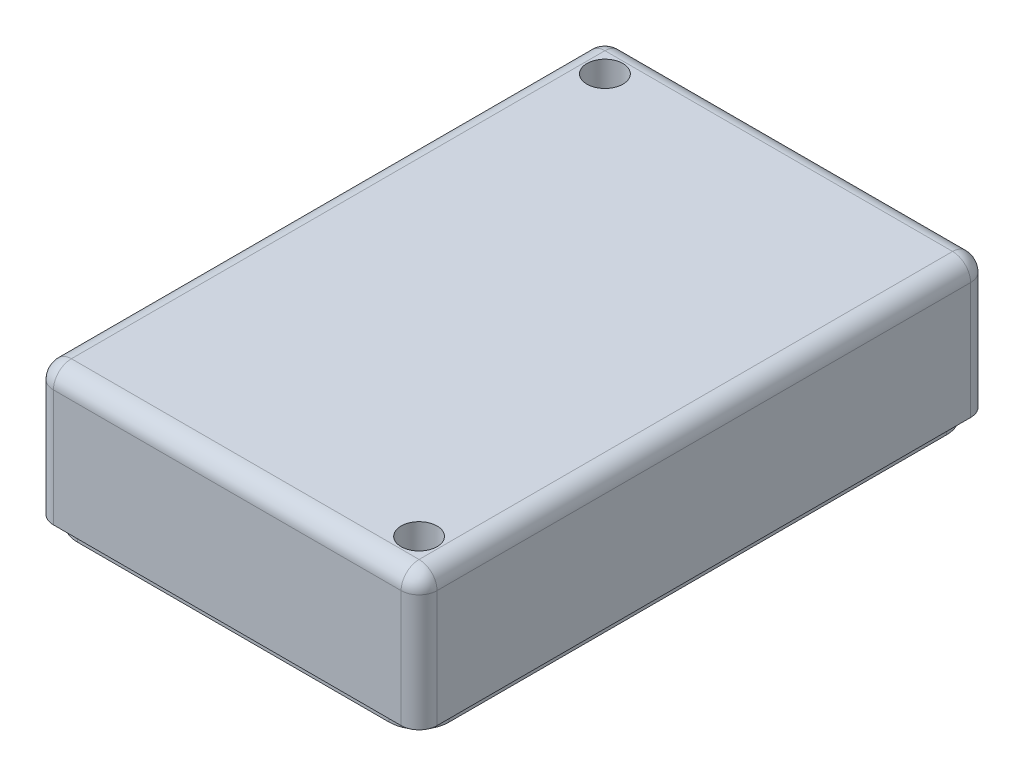
SolidWorks part; units mm, degrees
ref_plane "Front Plane" through (0, 0, 0) normal (0, 0, 1) x (1, 0, 0)
ref_plane "Top Plane" through (0, 0, 0) normal (0, 1, 0) x (1, 0, 0)
ref_plane "Right Plane" through (0, 0, 0) normal (1, 0, 0) x (0, 0, -1)
sketch "Sketch1" plane through (0, 0, 0) normal (0, 1, 0) x (1, 0, 0)
  line L5 (-32, -47.5) -> (32, -47.5)
  line L6 (-32, -47.5) -> (-32, 47.5)
  line L7 (-32, 47.5) -> (32, 47.5)
  line L8 (32, -47.5) -> (32, 47.5)
  line L9 (-32, -47.5) -> (32, 47.5) construction
  line L10 (-32, 47.5) -> (32, -47.5) construction
  point P0 (0, 0)
  dimension "D1" = 64
  dimension "D2" = 95
extrude "Boss-Extrude1" add sketch "Sketch1" along normal blind 2
sketch3d "3DSketch3"
  line L0 (-30, 0, 45.5) -> (-30, 0, -45.5)
  line L1 (-30, 0, -45.5) -> (30, 0, -45.5)
  line L2 (30, 0, -45.5) -> (30, 0, 45.5)
  line L3 (30, 0, 45.5) -> (-30, 0, 45.5)
  line L4 (-30, 0, 45.5) -> (-30, 0, -45.5)
  line L5 (-30, 0, -45.5) -> (30, 0, -45.5)
  line L6 (30, 0, -45.5) -> (30, 0, 45.5)
  line L7 (30, 0, 45.5) -> (-30, 0, 45.5)
  line L9 (-32, 0, 47.5) -> (-32, 0, -47.5)
  line L10 (-32, 0, 47.5) -> (32, 0, 47.5)
  line L11 (32, 0, 47.5) -> (32, 0, -47.5)
  line L12 (-32, 0, -47.5) -> (32, 0, -47.5)
  dimension "D1" = 2
extrude "Boss-Extrude2" add sketch "3DSketch3" along direction (0, -1, 0) on the side against the normal blind 22 contours L10 L9 L12 L11 | L4 L5 L6 L7
sketch3d "3DSketch4"
  line L0 (-31, -22, 46.5) -> (-31, -22, -46.5)
  line L1 (-32, -22, 47.5) -> (32, -22, 47.5)
  line L2 (-32, -22, 47.5) -> (-32, -22, -47.5)
  line L3 (-32, -22, -47.5) -> (32, -22, -47.5)
  line L4 (32, -22, 47.5) -> (32, -22, -47.5)
  line L5 (-31, -22, -46.5) -> (31, -22, -46.5)
  line L6 (31, -22, -46.5) -> (31, -22, 46.5)
  line L7 (31, -22, 46.5) -> (-31, -22, 46.5)
  line L8 (-31, -22, 46.5) -> (-31, -22, -46.5)
  line L9 (-31, -22, -46.5) -> (31, -22, -46.5)
  line L10 (31, -22, -46.5) -> (31, -22, 46.5)
  line L11 (31, -22, 46.5) -> (-31, -22, 46.5)
  dimension "D1" = 1
extrude "Cut-Extrude5" cut sketch "3DSketch4" along a picked direction on the side of the normal blind 1.5
fillet "Fillet1" radius 10 4 edges
sketch "Sketch3" plane through (0, 0, -47.5) normal (0, 0, -1) x (-1, 0, 0)
  line L0 (32, -20.5) -> (-32, -20.5) construction
  circle A0 centre (0, -20.5) radius 4
extrude "Cut-Extrude6" cut sketch "Sketch3" against normal up to next
sketch "Sketch4" plane through (0, 0, 0) normal (0, -1, 0) x (-1, 0, 0)
  line L0 (12.75, 37.0679) -> (12.75, 40.5679)
  line L5 (12.75, 40.5679) -> (-22.75, 40.5679)
  line L6 (-22.75, 37.0679) -> (-22.75, 40.5679)
  line L7 (12.75, 37.0679) -> (-22.75, 37.0679)
  line L8 (15.25, 34.5679) -> (-25.25, 34.5679)
  line L9 (-25.25, 34.5679) -> (-25.25, 43.0679)
  line L10 (15.25, 43.0679) -> (-25.25, 43.0679)
  line L11 (15.25, 34.5679) -> (15.25, 43.0679)
  dimension "D2" = 2.5
extrude "Boss-Extrude3" add sketch "Sketch4" along normal blind 20.5
sketch "Sketch5" plane through (0, 0, 0) normal (0, -1, 0) x (-1, 0, 0)
  line L1 (12.75, 37.0679) -> (-22.75, 37.0679)
  line L2 (12.75, 37.0679) -> (12.75, 40.5679)
  line L3 (12.75, 40.5679) -> (-22.75, 40.5679)
  line L4 (-22.75, 37.0679) -> (-22.75, 40.5679)
extrude "Boss-Extrude4" add sketch "Sketch5" along normal blind 11.4
sketch "Sketch6" plane through (0, 0, -34.5679) normal (0, 0, 1) x (1, 0, 0)
  line L0 (25.25, -20.5) -> (-15.25, -20.5) construction
  line L1 (15.25, -20.5) -> (-4.75, -20.5)
  line L2 (15.25, -20.5) -> (15.25, -16)
  line L3 (15.25, -16) -> (-4.75, -16)
  line L4 (-4.75, -20.5) -> (-4.75, -16)
  line L6 (-15.25, -20.5) -> (-15.25, 0) construction
  dimension "D1" = 10.5
  dimension "D2" = 20
  dimension "D3" = 4.5
extrude "Cut-Extrude7" cut sketch "Sketch6" against normal up to surface (8.5 mm away) up to face at (5, -10.25, -43.0679)
chamfer "Chamfer2" distance 4.2 angle 45 1 edges at (15.25, -20.5, -35.8179)
sketch "Sketch8" plane through (0, 2, 0) normal (0, 1, 0) x (1, 0, 0)
  line L5 (31, -46.5) -> (16, -31.5) construction
  line L10 (-31, 46.5) -> (-16, 31.5) construction
  circle A0 centre (-25.6575, 41.1575) radius 3
  circle A1 centre (-25.6575, 41.1575) radius 5
  circle A4 centre (25.6575, -41.1575) radius 5
  circle A5 centre (25.6575, -41.1575) radius 3
  point P0 (0, 0)
  dimension "D3" = 21.9203
  dimension "D1" = 48.5
  dimension "D2" = 48.5
extrude "Boss-Extrude6" add sketch "Sketch8" against normal up to surface (24 mm away) up to face at (0.4635, -22, -11.5)
sketch "Sketch9" plane through (0, -22, 0) normal (0, -1, 0) x (1, 0, 0)
sketch "Sketch10" plane through (0, -22, 0) normal (0, -1, 0) x (1, 0, 0)
  circle A0 centre (-25.6575, -41.1575) radius 3
  circle A1 centre (25.6575, 41.1575) radius 3
extrude "Cut-Extrude9" cut sketch "Sketch10" against normal up to surface (24 mm away) up to face at (0, 2, 0)
sketch "Sketch11" plane through (0, -22, 0) normal (0, -1, 0) x (1, 0, 0)
  circle A0 centre (25.6575, 41.1575) radius 3
  circle A1 centre (-25.6575, -41.1575) radius 3
extrude "Boss-Extrude7" add sketch "Sketch11" against normal blind 4
sketch "Sketch12" plane through (0, -22, 0) normal (0, -1, 0) x (1, 0, 0)
  circle A0 centre (25.6575, 41.1575) radius 1.5
  circle A1 centre (-25.6575, -41.1575) radius 1.5
extrude "Cut-Extrude10" cut sketch "Sketch12" against normal blind 4
fillet "Fillet2" radius 3 4 edges
fillet "Fillet3" radius 3 8 edges at (-32, 2, 0) (-31.1213, 2, -46.6213) (0, 2, -47.5) (31.1213, 2, -46.6213) (32, 2, 0) (31.1213, 2, 46.6213) (0, 2, 47.5) (-31.1213, 2, 46.6213)
sketch "Sketch13" plane through (0, 0, 0) normal (0, -1, 0) x (1, 0, 0)
  line L0 (15.25, -43.0679) -> (25.25, -43.0679) construction
  line L1 (20.25, -43.0679) -> (17.25, -43.0679)
  line L2 (20.25, -43.0679) -> (20.25, -45.5)
  line L3 (20.25, -45.5) -> (17.25, -45.5)
  line L4 (17.25, -43.0679) -> (17.25, -45.5)
  line L5 (-20, -45.5) -> (20, -45.5) construction
  line L6 (-20, -45.5) -> (-3.7081, -45.5) construction
  line L7 (-9.6939, -45.5) -> (-12.6939, -45.5)
  line L8 (-9.6939, -45.5) -> (-9.6939, -43.0679)
  line L9 (-9.6939, -43.0679) -> (-12.6939, -43.0679)
  line L10 (-12.6939, -45.5) -> (-12.6939, -43.0679)
  line L11 (-15.25, -43.0679) -> (-4.75, -43.0679) construction
  dimension "D1" = 3
  dimension "D2" = 3
extrude "Boss-Extrude8" add sketch "Sketch13" along normal up to surface (20.5 mm away) up to face at (-9.375, -20.5, -38.8179)
fillet "Fillet4" radius 1 4 edges at (-12.6939, -10.25, -45.5) (17.25, -10.25, -45.5) (20.25, -10.25, -45.4969) (-9.6939, -10.25, -45.5)
fillet "Fillet5" radius 2 3 edges at (-15.25, 0, -38.8179) (5, 0, -34.5679) (25.25, 0, -38.8179)
chamfer "Chamfer3" distance 1.7 angle 45 1 edges at (-25.6575, -18, -44.1575)
chamfer "Chamfer4" distance 1.7 angle 45 1 edges at (25.6575, -18, 38.1575)
fillet "Fillet6" radius 5 4 edges
